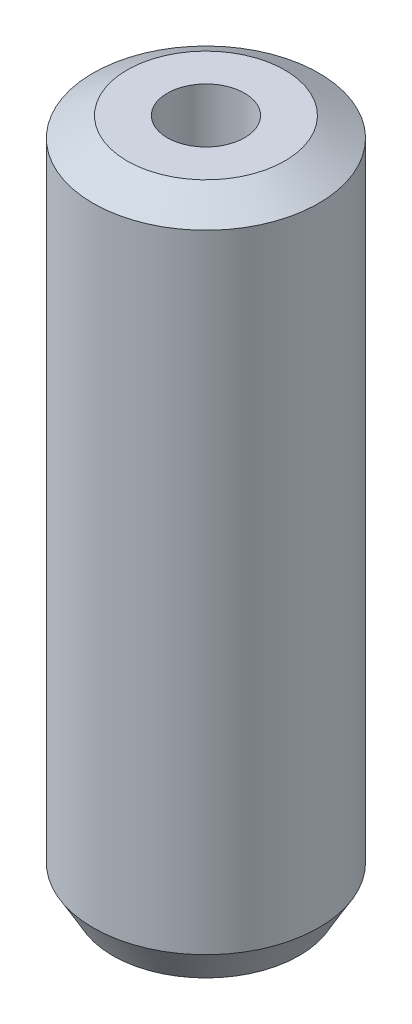
SolidWorks part; units mm, degrees
ref_plane "Front Plane" through (0, 0, 0) normal (0, 0, 1) x (1, 0, 0)
ref_plane "Top Plane" through (0, 0, 0) normal (0, 1, 0) x (1, 0, 0)
ref_plane "Right Plane" through (0, 0, 0) normal (1, 0, 0) x (0, 0, -1)
sketch "Sketch1" plane through (0, 0, 0) normal (0, 1, 0) x (1, 0, 0)
  circle A0 centre (0, 0) radius 17.5
  dimension "SHAFT_OD" = 35
extrude "Boss-Extrude1" add sketch "Sketch1" along normal blind 105.5947
sketch "Sketch2" plane through (0, 0, 0) normal (0, 1, 0) x (1, 0, 0)
  circle A0 centre (0, 0) radius 5.9924
  dimension "BORE_D" = 11.9848
extrude "Cut-Extrude1" cut sketch "Sketch2" along normal through all
chamfer "Chamfer1" distance 3.0446 angle 60 2 edges at (0, 105.5947, 17.5) (0, 0, 17.5) first distance on face at (0, 105.5947, 17.5) first distance on face at (0, 0, 5.9924)
